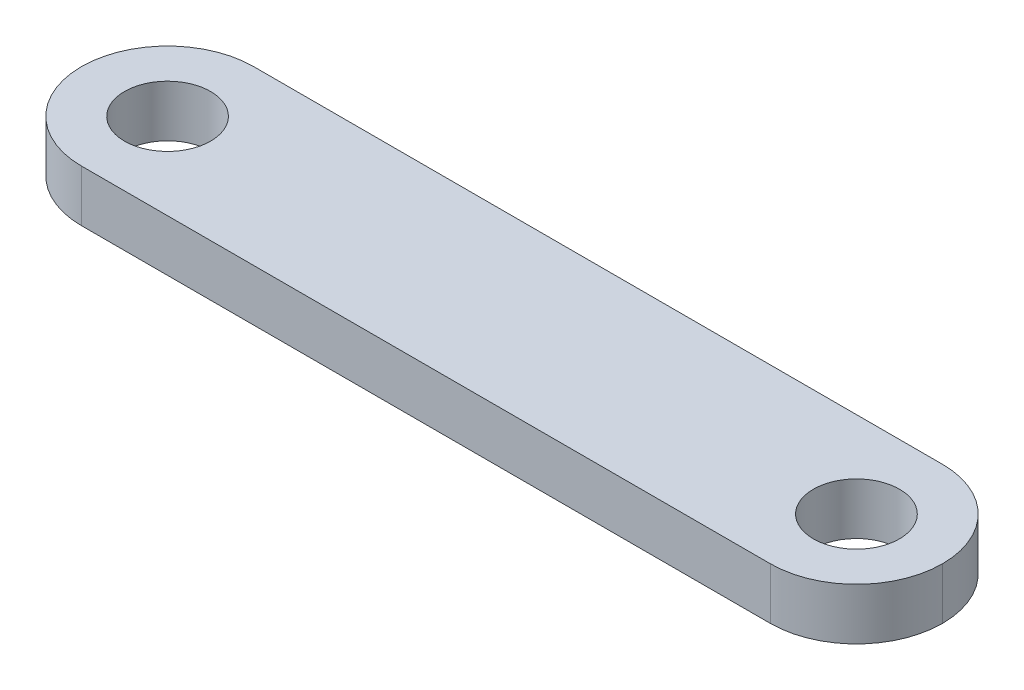
SolidWorks part; units mm, degrees
ref_plane "Front Plane" through (0, 0, 0) normal (0, 0, 1) x (1, 0, 0)
ref_plane "Top Plane" through (0, 0, 0) normal (0, 1, 0) x (1, 0, 0)
ref_plane "Right Plane" through (0, 0, 0) normal (1, 0, 0) x (0, 0, -1)
sketch "Sketch1" plane through (0, 0, 0) normal (0, 1, 0) x (1, 0, 0)
  line L1 (0, 0) -> (100, 0)
  line L2 (0, 0) -> (0, 20)
  line L3 (0, 20) -> (100, 20)
  line L4 (100, 0) -> (100, 20)
  dimension "D1" = 100
  dimension "D2" = 20
extrude "Boss-Extrude1" add sketch "Sketch1" along normal blind 6
fillet "Fillet1" radius 10 4 edges at (100, 3, -20) (100, 3, 0) (0, 3, -20) (0, 3, 0)
sketch "Sketch2" plane through (0, 6, 0) normal (0, 1, 0) x (1, 0, 0)
  circle A0 centre (10, 10) radius 5
  circle A1 centre (90, 10) radius 5
  point P6 (7.5, 7.5)
extrude "Cut-Extrude1" cut sketch "Sketch2" against normal through all
